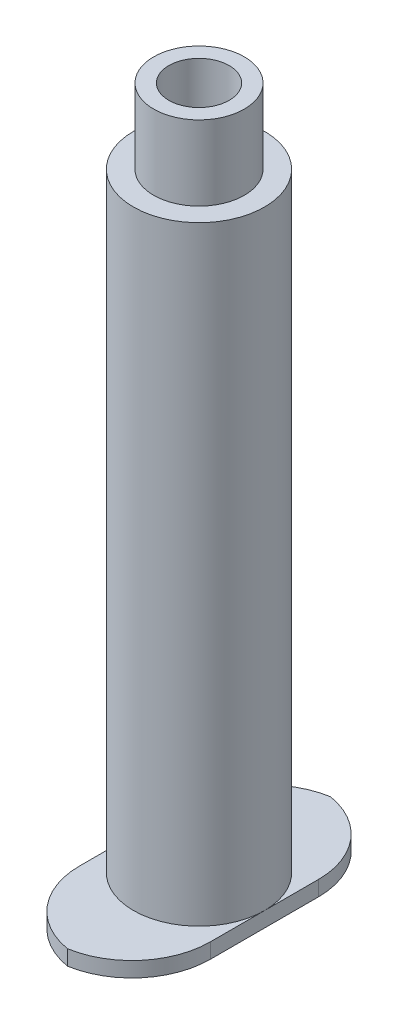
SolidWorks part; units mm, degrees
ref_plane "Alzado" through (0, 0, 0) normal (0, 0, 1) x (1, 0, 0)
ref_plane "Planta" through (0, 0, 0) normal (0, 1, 0) x (1, 0, 0)
ref_plane "Vista lateral" through (0, 0, 0) normal (1, 0, 0) x (0, 0, -1)
sketch "Croquis1" plane through (0, 0, 0) normal (0, 1, 0) x (1, 0, 0)
  circle A0 centre (0, 0) radius 6.67
  dimension "D1" = 13.34
extrude "Saliente-Extruir1" add sketch "Croquis1" along normal blind 62
sketch "Croquis2" plane through (0, 62, 0) normal (0, 1, 0) x (1, 0, 0)
  circle A0 centre (0, 0) radius 4.61
  dimension "D1" = 9.22
extrude "Saliente-Extruir2" add sketch "Croquis2" along normal blind 7.6
sketch "Croquis3" plane through (0, 0, 0) normal (0, -1, 0) x (1, 0, 0)
  circle A0 centre (0, 0) radius 5.13
  circle A1 centre (0, 0) radius 6.67 construction
  dimension "D1" = 1.54
extrude "Cortar-Extruir1" cut sketch "Croquis3" against normal blind 60.6
sketch "Croquis4" plane through (0, 69.6, 0) normal (0, 1, 0) x (1, 0, 0)
  circle A0 centre (0, 0) radius 3.07
  circle A1 centre (0, 0) radius 4.61 construction
  dimension "D1" = 1.54
extrude "Cortar-Extruir2" cut sketch "Croquis4" against normal blind 60.6
sketch "Croquis5" plane through (0, 0, 0) normal (0, -1, 0) x (1, 0, 0)
  line L1 (-6.67, 13.5) -> (6.67, 13.5)
  line L2 (-6.67, 13.5) -> (-6.67, -13.5)
  line L3 (-6.67, -13.5) -> (6.67, -13.5)
  line L4 (6.67, 13.5) -> (6.67, -13.5)
  line L5 (-6.67, 13.5) -> (6.67, -13.5) construction
  line L6 (-6.67, -13.5) -> (6.67, 13.5) construction
  circle A0 centre (0, 0) radius 5.13
  point P0 (0, 0)
  point P6 (-6.67, 0)
  dimension "D1" = 27
  dimension "D2" = 13.34
extrude "Saliente-Extruir3" add sketch "Croquis5" along normal blind 1.54
fillet "Redondeo1" radius 8 4 edges at (-6.67, -0.77, -13.5) (6.67, -0.77, -13.5) (-6.67, -0.77, 13.5) (6.67, -0.77, 13.5)
